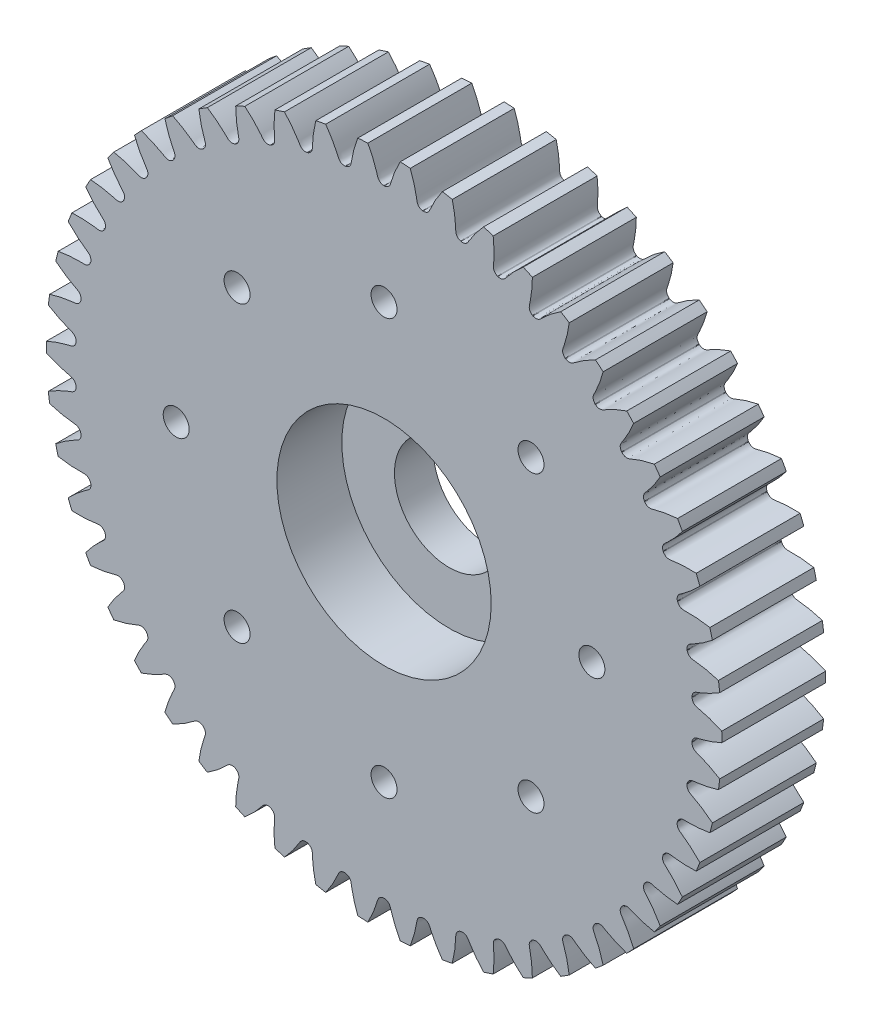
SolidWorks part; units mm, degrees
material "尼龙6"
ref_plane "前视基准面" through (0, 0, 0) normal (0, 0, 1) x (1, 0, 0)
ref_plane "上视基准面" through (0, 0, 0) normal (0, 1, 0) x (1, 0, 0)
ref_plane "右视基准面" through (0, 0, 0) normal (1, 0, 0) x (0, 0, -1)
sketch "草图1" plane through (0, 0, 0) normal (0, 0, 1) x (1, 0, 0)
  circle A0 centre (0, 0) radius 26
  circle A3 centre (0, 16) radius 1
  circle A4 centre (11.3137, 11.3137) radius 1
  circle A5 centre (16, 0) radius 1
  circle A6 centre (11.3137, -11.3137) radius 1
  circle A7 centre (0, -16) radius 1
  circle A8 centre (-11.3137, -11.3137) radius 1
  circle A9 centre (-16, 0) radius 1
  circle A10 centre (-11.3137, 11.3137) radius 1
  dimension "D1" = 52
  dimension "D2" = 2
  dimension "D3" = 16
extrude "凸台-拉伸1" add sketch "草图1" along normal blind 8
ref_axis "基准轴1" through (0, 0, -1.5) along (0, 0, 1)
sketch "草图2" plane through (0, 0, 0) normal (0, 0, 1) x (1, 0, 0)
  line L0 (0, 0) -> (0, 26) construction
  circle A0 centre (0, 0) radius 26 construction
  arc A1 (0.0183, 23.75) -> (-0.0183, 23.75) centre (0, 0) ccw
  arc A2 (3.8588, 29.4034) -> (-3.8588, 29.4034) centre (0, 0) ccw
  spline S0 degree 3 poles (0.0183, 23.75) (0.435, 23.8009) (0.4883, 24.1155) (0.5948, 24.4588) (0.6387, 24.5929) (0.6885, 24.735) (0.7445, 24.8848) (0.8068, 25.0423) (0.876, 25.2071) (0.9522, 25.3791) (1.0358, 25.5581) (1.1272, 25.7438) (1.2265, 25.9359) (1.3342, 26.1343) (1.4504, 26.3387) (1.5755, 26.5488) (1.7098, 26.7643) (1.8535, 26.985) (2.0068, 27.2105) (2.1701, 27.4406) (2.3435, 27.675) (2.5273, 27.9132) (2.7217, 28.1551) (2.9269, 28.4002) (3.1432, 28.6482) (3.4507, 28.9871) (3.6923, 29.2375) (3.8588, 29.4034) knots 0 0 0 0 0.116496 0.135538 0.155939 0.177697 0.200814 0.225289 0.251122 0.278313 0.306862 0.33677 0.368035 0.400659 0.434641 0.469981 0.506679 0.544736 0.584151 0.624923 0.667054 0.710544 0.755391 0.801596 0.84916 0.898082 1 1 1 1
  spline S1 degree 3 poles (-0.0183, 23.75) (-0.435, 23.8009) (-0.4883, 24.1155) (-0.5948, 24.4588) (-0.6387, 24.5929) (-0.6885, 24.735) (-0.7445, 24.8848) (-0.8068, 25.0423) (-0.876, 25.2071) (-0.9522, 25.3791) (-1.0358, 25.5581) (-1.1272, 25.7438) (-1.2265, 25.9359) (-1.3342, 26.1343) (-1.4504, 26.3387) (-1.5755, 26.5488) (-1.7098, 26.7643) (-1.8535, 26.985) (-2.0068, 27.2105) (-2.1701, 27.4406) (-2.3435, 27.675) (-2.5273, 27.9132) (-2.7217, 28.1551) (-2.9269, 28.4002) (-3.1432, 28.6482) (-3.4507, 28.9871) (-3.6923, 29.2375) (-3.8588, 29.4034) knots 0 0 0 0 0.116496 0.135538 0.155939 0.177697 0.200814 0.225289 0.251122 0.278313 0.306862 0.33677 0.368035 0.400659 0.434641 0.469981 0.506679 0.544736 0.584151 0.624923 0.667054 0.710544 0.755391 0.801596 0.84916 0.898082 1 1 1 1
extrude "切除-拉伸1" cut sketch "草图2" along normal through all
pattern_circular "阵列(圆周)1" count 50 every 7.2 about axis through (0, 0, -1.5) along (0, 0, 1) of "切除-拉伸1"
sketch "草图3" plane through (0, 0, 0) normal (0, 0, 1) x (1, 0, 0)
  circle A0 centre (0, 0) radius 25 construction
  dimension "Dn" = 50
sketch "草图4" plane through (0, 0, 8) normal (0, 0, 1) x (1, 0, 0)
  circle A0 centre (0, 0) radius 8.25
  dimension "D1" = 16.5
extrude "切除-拉伸2" cut sketch "草图4" against normal blind 5
sketch "草图5" plane through (0, 0, 3) normal (0, 0, 1) x (1, 0, 0)
  circle A0 centre (0, 0) radius 4.2
  dimension "D1" = 8.4
extrude "切除-拉伸3" cut sketch "草图5" against normal blind 4
